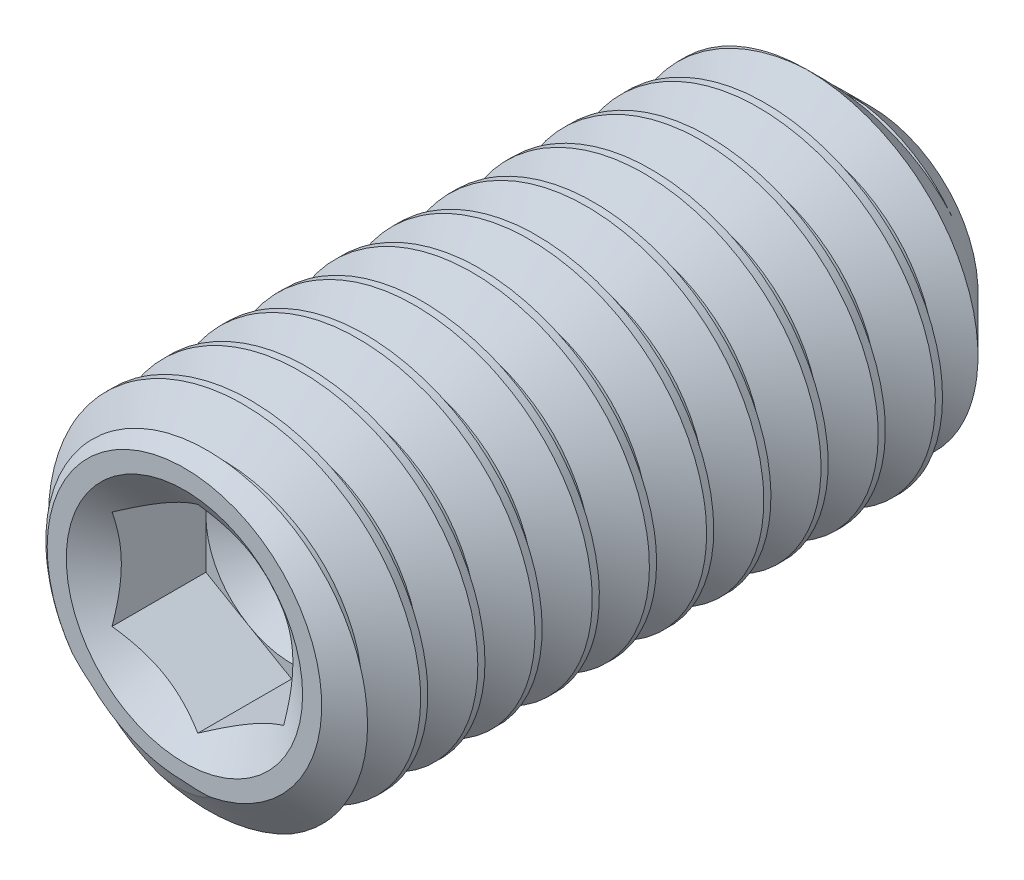
SolidWorks part; units mm, degrees
ref_plane "Front Plane" through (0, 0, 0) normal (0, 0, 1) x (1, 0, 0)
ref_plane "Top Plane" through (0, 0, 0) normal (0, 1, 0) x (1, 0, 0)
ref_plane "Right Plane" through (0, 0, 0) normal (1, 0, 0) x (0, 0, -1)
sketch "Sketch1" plane through (0, 0, 0) normal (1, 0, 0) x (0, 0, -1)
  line L0 (-2.7808, 0) -> (-2.7808, 1.2)
  line L1 (-2.7808, 1.2) -> (-2.5708, 1.5)
  line L2 (-2.5708, 1.5) -> (2.6567, 1.5)
  line L3 (2.6567, 1.5) -> (3.2192, 0.9375)
  line L5 (2.7808, 0) -> (-2.7808, 0)
  line L6 (2.7808, 0) -> (3.2192, 0) construction
  line L7 (3.2192, 0) -> (3.2192, 0.9375) construction
  line L8 (3.2192, -0.9375) -> (2.7808, 0) construction
  line L9 (-2.5708, -1.5) -> (2.6567, -1.5) construction
  line L10 (0, 0) -> (0, -0.5) construction
  line L11 (2.7808, 0) -> (3.112, 0.5512)
  line L12 (2.7808, 0) -> (3.112, -0.5512) construction
  arc A0 (3.112, 0.5512) -> (3.2192, 0.9375) centre (2.4692, 0.9375) ccw
  arc A1 (3.112, -0.5512) -> (3.2192, -0.9375) centre (2.4692, -0.9375) cw construction
  point P11 (-2.7808, 1.5)
  point P12 (1.4692, -1.5)
  point P13 (-1.5308, -1.5)
  point P14 (3.2192, 1.5)
  dimension "D5" = 0.75
  dimension "Thread Size" = 3
  dimension "Length" = 6
  dimension "D3" = 35
  dimension "D6" = 45
  dimension "D7" = 2.4
  dimension "Thread Pitch" = 0.5
  dimension "D2" = 1.25
  dimension "D4" = 59
  dimension "D8" = 1.875
  dimension "D1" = 1.75
sketch "Sketch2" plane through (0, 0, 0) normal (0, 0, 1) x (1, 0, 0)
  line L1 (0.75, 0.433) -> (0, 0.866) construction
  line L2 (0, 0.866) -> (-0.75, 0.433) construction
  line L3 (-0.75, 0.433) -> (-0.75, -0.433) construction
  line L4 (-0.75, -0.433) -> (0, -0.866) construction
  line L5 (0, -0.866) -> (0.75, -0.433) construction
  line L6 (0.75, -0.433) -> (0.75, 0.433) construction
  circle A0 centre (0, 0) radius 0.75 construction
  circle A1 centre (0, 0) radius 1.5 construction
  dimension "Drive Size" = 1.5
sketch "Sketch4" plane through (0, 0, 0) normal (1, 0, 0) x (0, 0, -1)
  line L0 (2.7808, 0) -> (3.112, 0.5512) construction
  line L1 (-2.5708, 1.5) -> (2.6567, 1.5) construction
  line L2 (-2.7808, 0) -> (-2.7808, 1.2) construction
  line L3 (2.7808, 0) -> (-2.7808, 0) construction
  line L4 (2.7808, 0) -> (3.112, 0.5512)
  line L5 (2.6567, 1.5) -> (3.2192, 0.9375) construction
  line L6 (2.6567, 1.5) -> (3.2192, 0.9375)
  line L8 (2.7808, 0) -> (-2.7808, 0)
  line L9 (-2.7808, 0) -> (-2.7808, 1.2)
  line L10 (-2.5708, 1.5) -> (2.6567, 1.5)
  line L11 (-2.7808, 1.2) -> (-2.5708, 1.5) construction
  line L12 (-2.7808, 1.2) -> (-2.5708, 1.5)
  arc A0 (3.112, 0.5512) -> (3.2192, 0.9375) centre (2.4692, 0.9375) ccw construction
  arc A1 (3.112, 0.5512) -> (3.2192, 0.9375) centre (2.4692, 0.9375) ccw
revolve "Revolve1" add sketch "Sketch4" angle 360 about L8
sketch "Sketch6" plane through (0, 0, 2.7808) normal (0, 0, 1) x (1, 0, 0)
  line L1 (0.75, 0.433) -> (0, 0.866)
  line L2 (0, 0.866) -> (-0.75, 0.433)
  line L3 (-0.75, 0.433) -> (-0.75, -0.433)
  line L4 (-0.75, -0.433) -> (0, -0.866)
  line L5 (0, -0.866) -> (0.75, -0.433)
  line L6 (0.75, -0.433) -> (0.75, 0.433)
  circle A0 centre (0, 0) radius 0.75 construction
  dimension "D1" = 1.5
extrude "Cut-Extrude3" cut sketch "Sketch6" against normal blind 0.9375
sketch "Sketch7" plane through (0, 0, 2.7808) normal (0, 0, 1) x (1, 0, 0)
  line L0 (0, 0.866) -> (0, 1.2) construction
  circle A0 centre (0, 0) radius 1.033
  circle A2 centre (0, 0) radius 1.2 construction
  point P6 (0, 1.033)
  point P10 (0, 1.033)
extrude "Cut-Extrude4" cut sketch "Sketch7" against normal through all draft 55
sketch "Sketch8" plane through (0, 0, 1.8433) normal (0, 0, 1) x (1, 0, 0)
  circle A0 centre (0, 0) radius 0.75 construction
  circle A1 centre (0, 0) radius 0.75
extrude "Cut-Extrude5" cut sketch "Sketch8" against normal through all draft 60
ref_plane "Plane1" through (0, 0, -3.2192) normal (0, 0, 1) x (1, 0, 0)
sketch "Sketch9" plane through (0, 0, -3.2192) normal (0, 0, 1) x (1, 0, 0)
  circle A0 centre (0, 0) radius 1.5 construction
  circle A1 centre (0, 0) radius 1.5
curve "Helix/Spiral1" pitch 0.5 height 6.5 radius 1.5 centre (0, 0, -3.2192) axis (0, 0, 1) start towards (0, 1, 0)
sketch "Sketch10" plane through (0, 0, 0) normal (1, 0, 0) x (0, 0, -1)
  line L0 (3.2192, 1.5) -> (3.6567, 1.5)
  line L1 (3.6567, 1.5) -> (3.4692, 1.1752)
  line L2 (3.4067, 1.1752) -> (3.2192, 1.5)
  line L3 (3.4067, 1.1752) -> (3.4692, 1.1752)
  line L4 (3.4379, 1.1752) -> (3.4379, 1.5) construction
  line L5 (3.3129, 1.3376) -> (3.5629, 1.3376) construction
  point P10 (3.4379, 1.3376)
  dimension "D1" = 60
  dimension "D2" = 0.0625
  dimension "D3" = 0.25
sweep "Cut-Sweep1" cut profiles "Sketch10" path "Helix/Spiral1"
equation "\"D7@Sketch1\" = \"Thread Size@Sketch1\" * .8"
equation "\"D3\"= \"Length@Sketch1\" + \"Thread Pitch@Sketch1\""
equation "\"D4\"= \"Thread Pitch@Sketch1\""
equation "\"D1@Sketch6\"=\"Drive Size@Sketch2\""
equation "\"D1@Cut-Extrude3\"=\"Drive Size@Sketch2\"*.625"
equation "\"D3@Helix/Spiral1\"=\"Length@Sketch1\"+\"Thread Pitch@Sketch1\""
equation "\"D4@Helix/Spiral1\"=\"Thread Pitch@Sketch1\""
equation "\"D2@Sketch10\"=\"Thread Pitch@Sketch1\"/8"
equation "\"D3@Sketch10\"=\"Thread Pitch@Sketch1\"/2"
equation "\"D2@Sketch1\"=\"Thread Pitch@Sketch1\"*2.5"
equation "\"D5@Sketch1\"=\"Thread Size@Sketch1\"*.25"
equation "\"D8@Sketch1\"=\"Thread Size@Sketch1\"*.625"
equation "\"D1@Sketch1\"=\"Thread Pitch@Sketch1\"*3.5"
